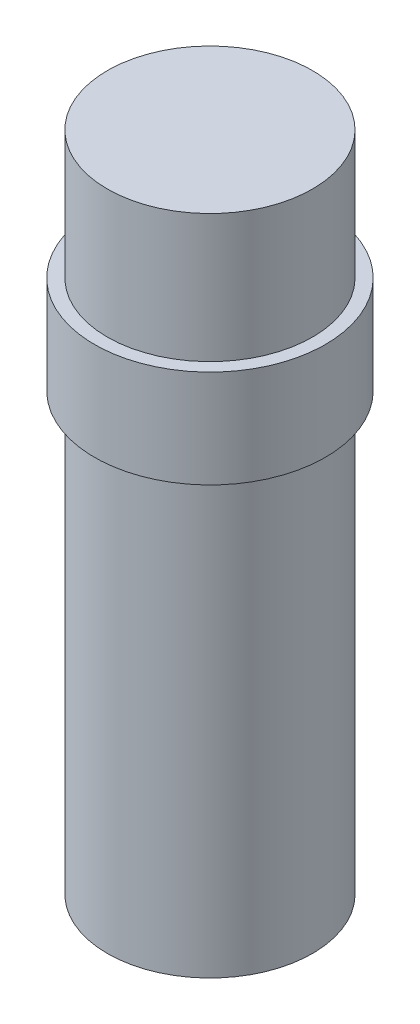
SolidWorks part; units mm, degrees
ref_plane "Front Plane" through (0, 0, 0) normal (0, 0, 1) x (1, 0, 0)
ref_plane "Top Plane" through (0, 0, 0) normal (0, 1, 0) x (1, 0, 0)
ref_plane "Right Plane" through (0, 0, 0) normal (1, 0, 0) x (0, 0, -1)
sketch "Sketch1" plane through (0, 0, 0) normal (0, 1, 0) x (1, 0, 0)
  circle A0 centre (0, 0) radius 4
  dimension "D1" = 8
extrude "Boss-Extrude1" add sketch "Sketch1" along normal blind 17
sketch "Sketch2" plane through (0, 17, 0) normal (0, 1, 0) x (1, 0, 0)
  circle A0 centre (0, 0) radius 4.5
  dimension "D1" = 9
extrude "Boss-Extrude2" add sketch "Sketch2" along normal blind 3.81
sketch "Sketch3" plane through (0, 20.81, 0) normal (0, 1, 0) x (1, 0, 0)
  circle A0 centre (0, 0) radius 4
  dimension "D1" = 8
extrude "Boss-Extrude3" add sketch "Sketch3" along normal blind 5
